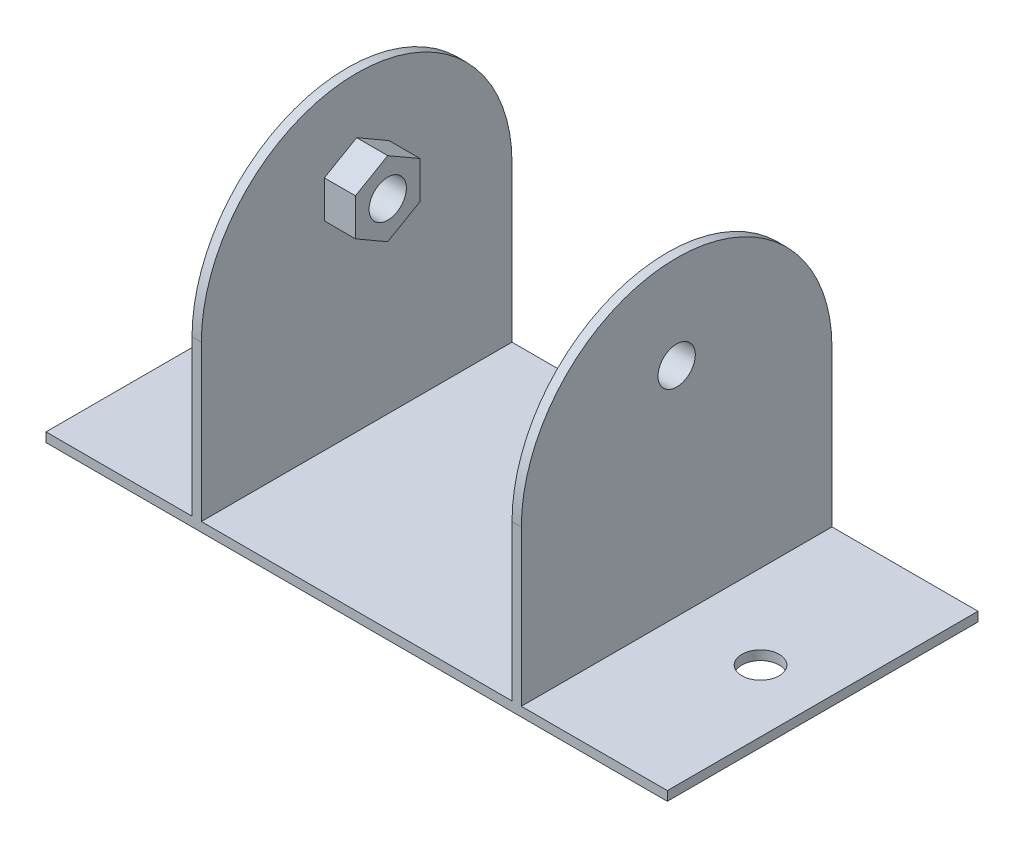
SolidWorks part; units mm, degrees
ref_plane "Front Plane" through (0, 0, 0) normal (0, 0, 1) x (1, 0, 0)
ref_plane "Top Plane" through (0, 0, 0) normal (0, 1, 0) x (1, 0, 0)
ref_plane "Right Plane" through (0, 0, 0) normal (1, 0, 0) x (0, 0, -1)
sketch "Sketch1" plane through (0, 0, 0) normal (0, 0, 1) x (1, 0, 0)
  line L5 (50, -1.5) -> (-50, -1.5)
  line L9 (-50, -1.5) -> (-50, 0)
  line L10 (-50, 0) -> (-26.5, 0)
  line L11 (-26.5, 0) -> (-26.5, 50)
  line L12 (-26.5, 50) -> (-25, 50)
  line L13 (-25, 50) -> (-25, 0)
  line L14 (-25, 0) -> (25, 0)
  line L15 (0, 0) -> (0, 32.1698) construction
  line L16 (50, -1.5) -> (50, 0)
  line L17 (26.5, 50) -> (25, 50)
  line L18 (26.5, 0) -> (26.5, 50)
  line L19 (25, 50) -> (25, 0)
  line L20 (50, 0) -> (26.5, 0)
  point P11 (0, -1.5)
  dimension "D1" = 1.5
  dimension "D2" = 1.5
  dimension "D3" = 100
  dimension "D4" = 50
  dimension "D5" = 50
extrude "Boss-Extrude1" add sketch "Sketch1" along normal blind 50
sketch "Sketch2" plane through (0, 0, 0) normal (0, 1, 0) x (1, 0, 0)
  line L0 (-50, -25) -> (50, -25) construction
  line L1 (-50, -50) -> (-50, 0) construction
  line L2 (50, -50) -> (50, 0) construction
  line L3 (0, 0) -> (0, -50) construction
  line L4 (25, -50) -> (-25, -50) construction
  circle A0 centre (-40, -25) radius 3
  circle A1 centre (40, -25) radius 3
  dimension "D1" = 80
  dimension "D2" = 6
extrude "Cut-Extrude1" cut sketch "Sketch2" against normal up to next
sketch "Sketch3" plane through (-26.5, 0, 0) normal (-1, 0, 0) x (0, 0, 1)
  line L0 (25, 50) -> (25, 0) construction
  line L1 (50, 50) -> (0, 50) construction
  line L2 (50, 0) -> (0, 0) construction
  circle A0 centre (25, 35) radius 3
  dimension "D2" = 6
  dimension "D1" = 15
extrude "Cut-Extrude2" cut sketch "Sketch3" against normal blind 70
fillet "Fillet2" 2 edges at (25.75, 50, 0) (25.75, 50, 50) type full round first side face at (0, 16.4167, 0) second side face at (0, 16.4167, 50) middle face at (25.75, 50, 25)
fillet "Fillet3" 2 edges at (-25.75, 50, 50) (-25.75, 50, 0) type full round first side face at (0, 12.25, 50) second side face at (0, 12.25, 0) middle face at (-25.75, 50, 25)
sketch "Sketch4" plane through (-25, 0, 0) normal (1, 0, 0) x (0, 0, -1)
  line L0 (-50, 0) -> (-50, 25) construction
  line L1 (-30.1962, 32) -> (-25, 29)
  line L2 (-25, 29) -> (-19.8038, 32)
  line L3 (-19.8038, 32) -> (-19.8038, 38)
  line L4 (-19.8038, 38) -> (-25, 41)
  line L5 (-25, 41) -> (-30.1962, 38)
  line L6 (-30.1962, 38) -> (-30.1962, 32)
  circle A0 centre (-25, 35) radius 5.1962 construction
  circle A1 centre (-25, 35) radius 3
  dimension "D1" = 6
extrude "Boss-Extrude2" add sketch "Sketch4" along normal blind 5
mirror "Mirror1" about plane through (0, 0, 0) normal (1, 0, 0) of "Boss-Extrude2"
